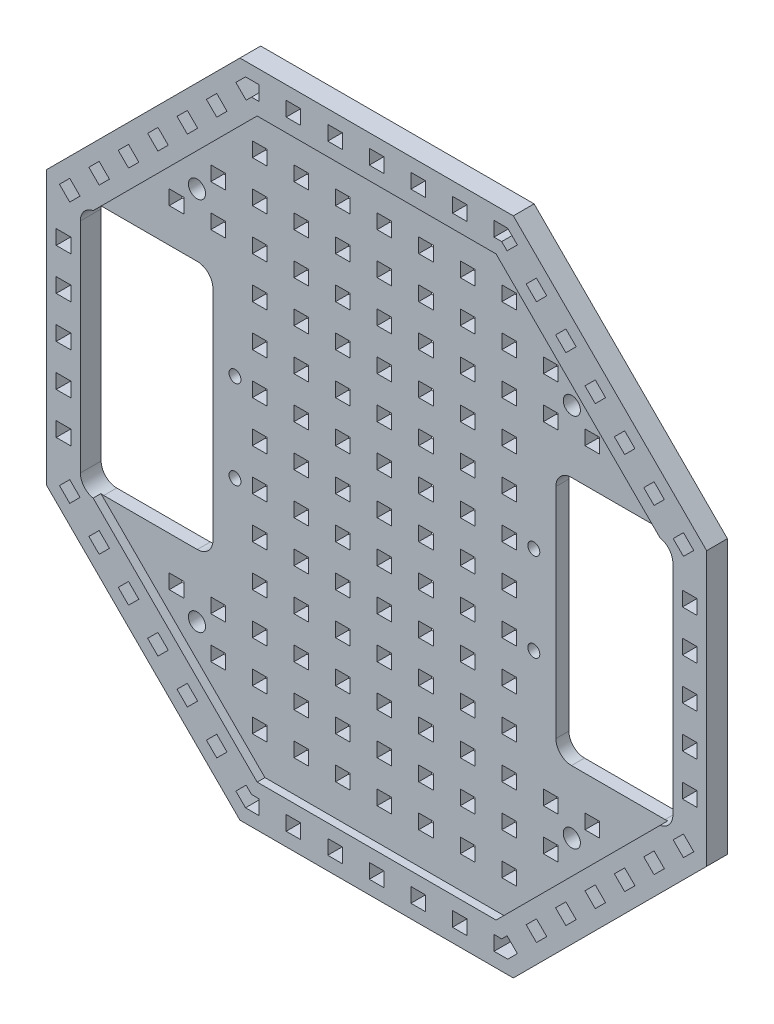
SolidWorks part; units mm, degrees
ref_plane "Plano frontal" through (0, 0, 0) normal (0, 0, 1) x (1, 0, 0)
ref_plane "Plano superior" through (0, 0, 0) normal (0, 1, 0) x (1, 0, 0)
ref_plane "Plano direito" through (0, 0, 0) normal (1, 0, 0) x (0, 0, -1)
sketch "Esboço1" plane through (0, 0, 0) normal (0, 0, 1) x (1, 0, 0)
  line L1 (63.5, -26.3026) -> (63.5, 26.3026)
  line L2 (63.5, 26.3026) -> (26.3026, 63.5)
  line L3 (26.3026, 63.5) -> (-26.3026, 63.5)
  line L4 (-26.3026, 63.5) -> (-63.5, 26.3026)
  line L5 (-63.5, 26.3026) -> (-63.5, -26.3026)
  line L6 (-63.5, -26.3026) -> (-26.3026, -63.5)
  line L7 (-26.3026, -63.5) -> (26.3026, -63.5)
  line L8 (26.3026, -63.5) -> (63.5, -26.3026)
  circle A0 centre (0, 0) radius 63.5 construction
  dimension "D1" = 127
extrude "Ressalto-extrusão1" add sketch "Esboço1" along normal blind 2.5
sketch "Esboço3"
sketch "Esboço2" plane through (0, 0, 0) normal (0, 0, -1) x (-1, 0, 0)
  line L0 (-45, 0) -> (45, 0) construction
  line L1 (-28.75, 0) -> (28.75, 0) construction
  line L2 (28.75, 0) -> (28.75, 8.5) construction
  line L3 (0, 0) -> (0, 75.734) construction
  line L4 (54, 24) -> (36, 24)
  line L5 (57, 21) -> (57, -21)
  line L6 (54, -24) -> (36, -24)
  line L7 (33, 21) -> (33, -21)
  line L8 (57, 24) -> (33, -24) construction
  line L9 (57, -24) -> (33, 24) construction
  line L10 (-57, -24) -> (-33, 24) construction
  line L11 (-57, 24) -> (-33, -24) construction
  line L12 (-28.75, 0) -> (-28.75, 8.5) construction
  line L13 (-33, 21) -> (-33, -21)
  line L14 (-54, -24) -> (-36, -24)
  line L15 (-57, 21) -> (-57, -21)
  line L16 (-54, 24) -> (-36, 24)
  line L17 (0, 0) -> (0, -57) construction
  circle A0 centre (28.75, 8.5) radius 1.15
  circle A1 centre (28.75, -8.5) radius 1.15
  arc A2 (36, 24) -> (33, 21) centre (36, 21) ccw
  arc A3 (36, -24) -> (33, -21) centre (36, -21) cw
  arc A4 (57, -21) -> (54, -24) centre (54, -21) cw
  arc A5 (54, 24) -> (57, 21) centre (54, 21) cw
  arc A6 (-54, 24) -> (-57, 21) centre (-54, 21) ccw
  arc A7 (-57, -21) -> (-54, -24) centre (-54, -21) ccw
  arc A8 (-36, -24) -> (-33, -21) centre (-36, -21) ccw
  arc A9 (-36, 24) -> (-33, 21) centre (-36, 21) cw
  circle A10 centre (-28.75, -8.5) radius 1.15
  circle A11 centre (-28.75, 8.5) radius 1.15
  dimension "D6" = 3
  dimension "D1" = 45
  dimension "D2" = 48
  dimension "D3" = 24
  dimension "D4" = 28.75
  dimension "D5" = 8.5
  dimension "D7" = 57
extrude "Corte-extrusão1" cut sketch "Esboço2" against normal through all
sketch "Esboço4" plane through (0, 0, 0) normal (0, 0, -1) x (-1, 0, 0)
  line L0 (0, 0) -> (36.0624, 36.0624) construction
  circle A0 centre (0, 0) radius 51 construction
  circle A1 centre (36.0624, -36.0624) radius 1.65
  circle A2 centre (36.0624, 36.0624) radius 1.65
  circle A3 centre (-36.0624, -36.0624) radius 1.65
  circle A4 centre (-36.0624, 36.0624) radius 1.65
  point P7 (0, 0)
  point P14 (0, 0)
  point P15 (0, 0)
  dimension "D1" = 4
extrude "Corte-extrusão2" cut sketch "Esboço4" against normal blind 40.5
sketch "Esboço5" plane through (0, 0, 2.5) normal (0, 0, 1) x (1, 0, 0)
  line L0 (23.6102, -57) -> (57, -23.6102) construction
  line L1 (57, -21) -> (57, 21)
  line L2 (57, 23.6102) -> (23.6102, 57) construction
  line L3 (23.6102, 57) -> (-23.6102, 57) construction
  line L4 (-23.6102, 57) -> (-57, 23.6102) construction
  line L5 (-57, 21) -> (-57, -21)
  line L6 (-57, -23.6102) -> (-23.6102, -57) construction
  line L7 (-23.6102, -57) -> (23.6102, -57) construction
  line L8 (26.3026, -63.5) -> (63.5, -26.3026)
  line L9 (63.5, -26.3026) -> (63.5, 26.3026)
  line L10 (63.5, 26.3026) -> (26.3026, 63.5)
  line L11 (26.3026, 63.5) -> (-26.3026, 63.5)
  line L12 (-26.3026, 63.5) -> (-63.5, 26.3026)
  line L13 (-63.5, 26.3026) -> (-63.5, -26.3026)
  line L14 (-63.5, -26.3026) -> (-26.3026, -63.5)
  line L15 (-26.3026, -63.5) -> (26.3026, -63.5)
  line L16 (26.3026, -63.5) -> (63.5, -26.3026)
  line L17 (63.5, -26.3026) -> (63.5, 26.3026)
  line L18 (63.5, 26.3026) -> (26.3026, 63.5)
  line L19 (26.3026, 63.5) -> (-26.3026, 63.5)
  line L20 (-26.3026, 63.5) -> (-63.5, 26.3026)
  line L21 (-63.5, 26.3026) -> (-63.5, -26.3026)
  line L22 (-63.5, -26.3026) -> (-26.3026, -63.5)
  line L23 (-26.3026, -63.5) -> (26.3026, -63.5)
  line L24 (-22.9889, 55.5) -> (-54.5374, 23.9515)
  line L25 (-22.9889, 55.5) -> (-55.5, 22.9889) construction
  line L26 (-54.5374, -23.9515) -> (-22.9889, -55.5)
  line L27 (-22.9889, -55.5) -> (22.9889, -55.5)
  line L28 (22.9889, -55.5) -> (54.5374, -23.9515)
  line L29 (-55.5, -22.9889) -> (-22.9889, -55.5) construction
  line L30 (54.5374, 23.9515) -> (22.9889, 55.5)
  line L31 (22.9889, 55.5) -> (-22.9889, 55.5)
  line L32 (22.9889, -55.5) -> (55.5, -22.9889) construction
  line L33 (57, -23.6102) -> (57, 23.6102) construction
  line L34 (55.5, 22.9889) -> (22.9889, 55.5) construction
  line L35 (55.5, -22.9889) -> (55.5, 22.9889) construction
  line L43 (-55.5, 22.9889) -> (-55.5, -22.9889) construction
  line L44 (-57, 23.6102) -> (-57, -23.6102) construction
  arc A2 (54.5374, -23.9515) -> (57, -21) centre (54, -21) ccw
  arc A3 (57, 21) -> (54.5374, 23.9515) centre (54, 21) ccw
  arc A5 (-54.5374, 23.9515) -> (-57, 21) centre (-54, 21) ccw
  arc A7 (-57, -21) -> (-54.5374, -23.9515) centre (-54, -21) ccw
  dimension "D1" = 0
  dimension "D2" = 6.5
  dimension "D3" = 1.5
extrude "Ressalto-extrusão2" add sketch "Esboço5" along normal blind 1.5
sketch "Esboço6" plane through (0, 0, 0) normal (0, 0, -1) x (-1, 0, 0)
  line L0 (-44.9013, -44.9013) -> (-42.0729, -42.0729) construction
  line L1 (-47.7297, -34.4361) -> (-49.7096, -36.416)
  line L2 (-42.0729, -40.093) -> (-44.0528, -42.0729)
  line L3 (-42.0729, -40.093) -> (-40.093, -42.0729)
  line L4 (-40.093, -42.0729) -> (-42.0729, -44.0528)
  line L5 (-44.0528, -42.0729) -> (-42.0729, -44.0528)
  line L6 (-42.0729, -40.093) -> (-42.0729, -44.0528) construction
  line L7 (-40.093, -42.0729) -> (-44.0528, -42.0729) construction
  line L8 (-47.7297, -34.4361) -> (-45.7498, -36.416)
  line L9 (-45.7498, -36.416) -> (-47.7297, -38.3959)
  line L10 (-49.7096, -36.416) -> (-47.7297, -38.3959)
  line L11 (-47.7297, -34.4361) -> (-47.7297, -38.3959) construction
  line L12 (-45.7498, -36.416) -> (-49.7096, -36.416) construction
  line L13 (-53.3866, -28.7792) -> (-55.3665, -30.7591)
  line L14 (-53.3866, -28.7792) -> (-51.4067, -30.7591)
  line L15 (-51.4067, -30.7591) -> (-53.3866, -32.739)
  line L16 (-55.3665, -30.7591) -> (-53.3866, -32.739)
  line L17 (-53.3866, -28.7792) -> (-53.3866, -32.739) construction
  line L18 (-51.4067, -30.7591) -> (-55.3665, -30.7591) construction
  line L19 (-59.0434, -23.1224) -> (-61.0233, -25.1023)
  line L20 (-59.0434, -23.1224) -> (-57.0635, -25.1023)
  line L21 (-57.0635, -25.1023) -> (-59.0434, -27.0822)
  line L22 (-61.0233, -25.1023) -> (-59.0434, -27.0822)
  line L23 (-59.0434, -23.1224) -> (-59.0434, -27.0822) construction
  line L24 (-57.0635, -25.1023) -> (-61.0233, -25.1023) construction
  line L25 (-63.5, 0) -> (-57, 0) construction
  line L26 (-30.7591, -51.4067) -> (-30.7591, -55.3665) construction
  line L27 (-28.7792, -53.3866) -> (-32.739, -53.3866) construction
  line L28 (-36.416, -45.7498) -> (-36.416, -49.7096) construction
  line L29 (-34.4361, -47.7297) -> (-38.3959, -47.7297) construction
  line L30 (-42.0729, -40.093) -> (-42.0729, -44.0528) construction
  line L31 (-40.093, -42.0729) -> (-44.0528, -42.0729) construction
  line L32 (-25.2256, -60.9) -> (-27.0822, -59.0434)
  line L33 (-25.1023, -57.0635) -> (-27.0822, -59.0434)
  line L34 (-58.85, -6.6) -> (-61.65, -6.6)
  line L35 (-30.7591, -55.3665) -> (-32.739, -53.3866)
  line L36 (-30.7591, -51.4067) -> (-32.739, -53.3866)
  line L37 (-28.7792, -53.3866) -> (-30.7591, -51.4067)
  line L38 (-28.7792, -53.3866) -> (-30.7591, -55.3665)
  line L39 (-36.416, -49.7096) -> (-38.3959, -47.7297)
  line L40 (-36.416, -45.7498) -> (-38.3959, -47.7297)
  line L41 (-34.4361, -47.7297) -> (-36.416, -45.7498)
  line L42 (-34.4361, -47.7297) -> (-36.416, -49.7096)
  line L43 (0, -63.5) -> (0, -59.5) construction
  line L44 (-6.6, -58.1) -> (-9.4, -58.1)
  line L45 (1.4, -58.1) -> (-1.4, -58.1)
  line L46 (1.4, -58.1) -> (1.4, -60.9)
  line L47 (1.4, -60.9) -> (-1.4, -60.9)
  line L48 (-1.4, -58.1) -> (-1.4, -60.9)
  line L49 (1.4, -58.1) -> (-1.4, -60.9) construction
  line L50 (1.4, -60.9) -> (-1.4, -58.1) construction
  line L51 (-6.6, -58.1) -> (-6.6, -60.9)
  line L52 (-6.6, -60.9) -> (-9.4, -60.9)
  line L53 (-9.4, -58.1) -> (-9.4, -60.9)
  line L54 (-6.6, -58.1) -> (-9.4, -60.9) construction
  line L55 (-6.6, -60.9) -> (-9.4, -58.1) construction
  line L56 (-14.6, -58.1) -> (-17.4, -58.1)
  line L57 (-14.6, -58.1) -> (-14.6, -60.9)
  line L58 (-14.6, -60.9) -> (-17.4, -60.9)
  line L59 (-17.4, -58.1) -> (-17.4, -60.9)
  line L60 (-14.6, -58.1) -> (-17.4, -60.9) construction
  line L61 (-14.6, -60.9) -> (-17.4, -58.1) construction
  line L62 (-22.6, -58.1) -> (-24.0658, -58.1)
  line L63 (-22.6, -58.1) -> (-22.6, -60.9)
  line L64 (-22.6, -60.9) -> (-25.2256, -60.9)
  line L65 (-58.85, 1.4) -> (-61.65, 1.4)
  line L66 (-58.85, 1.4) -> (-58.85, -1.4)
  line L67 (-58.85, -1.4) -> (-61.65, -1.4)
  line L68 (-61.65, 1.4) -> (-61.65, -1.4)
  line L69 (-58.85, 1.4) -> (-61.65, -1.4) construction
  line L70 (58.85, -17.4) -> (61.65, -14.6) construction
  line L71 (9.4, 1.4) -> (6.6, -1.4) construction
  line L72 (16, 24) -> (0, 24) construction
  line L73 (0, 24) -> (-16, 24) construction
  line L74 (-24.0658, -58.1) -> (-25.1023, -57.0635)
  line L75 (6.6, 25.4) -> (6.6, 22.6)
  line L76 (9.4, 22.6) -> (6.6, 22.6)
  line L77 (-25.4, 46.6) -> (-22.6, 49.4) construction
  line L78 (9.4, 25.4) -> (6.6, 22.6) construction
  line L79 (-58.85, -1.4) -> (-61.65, 1.4) construction
  line L80 (-58.85, -6.6) -> (-58.85, -9.4)
  line L81 (-58.85, -9.4) -> (-61.65, -9.4)
  line L82 (-61.65, -6.6) -> (-61.65, -9.4)
  line L83 (-58.85, -6.6) -> (-61.65, -9.4) construction
  line L84 (-58.85, -9.4) -> (-61.65, -6.6) construction
  line L85 (-58.85, -14.6) -> (-61.65, -14.6)
  line L86 (-58.85, -14.6) -> (-58.85, -17.4)
  line L87 (-58.85, -17.4) -> (-61.65, -17.4)
  line L88 (-61.65, -14.6) -> (-61.65, -17.4)
  line L89 (-58.85, -14.6) -> (-61.65, -17.4) construction
  line L90 (-58.85, -17.4) -> (-61.65, -14.6) construction
  line L91 (9.4, 22.6) -> (6.6, 25.4) construction
  line L92 (0, 0) -> (0, 63.5) construction
  line L93 (-25.4, 49.4) -> (-22.6, 46.6) construction
  line L94 (58.85, -14.6) -> (61.65, -17.4) construction
  line L95 (58.85, -9.4) -> (61.65, -6.6) construction
  line L96 (58.85, -6.6) -> (61.65, -9.4) construction
  line L97 (58.85, -1.4) -> (61.65, 1.4) construction
  line L98 (58.85, 1.4) -> (61.65, -1.4) construction
  line L99 (14.6, -60.9) -> (17.4, -58.1) construction
  line L100 (14.6, -58.1) -> (17.4, -60.9) construction
  line L101 (6.6, -60.9) -> (9.4, -58.1) construction
  line L102 (6.6, -58.1) -> (9.4, -60.9) construction
  line L103 (40.093, -42.0729) -> (44.0528, -42.0729) construction
  line L104 (42.0729, -40.093) -> (42.0729, -44.0528) construction
  line L105 (34.4361, -47.7297) -> (38.3959, -47.7297) construction
  line L106 (36.416, -45.7498) -> (36.416, -49.7096) construction
  line L107 (28.7792, -53.3866) -> (32.739, -53.3866) construction
  line L108 (30.7591, -51.4067) -> (30.7591, -55.3665) construction
  line L109 (63.5, 0) -> (57, 0) construction
  line L110 (57.0635, -25.1023) -> (61.0233, -25.1023) construction
  line L111 (59.0434, -23.1224) -> (59.0434, -27.0822) construction
  line L112 (51.4067, -30.7591) -> (55.3665, -30.7591) construction
  line L113 (53.3866, -28.7792) -> (53.3866, -32.739) construction
  line L114 (45.7498, -36.416) -> (49.7096, -36.416) construction
  line L115 (47.7297, -34.4361) -> (47.7297, -38.3959) construction
  line L116 (40.093, -42.0729) -> (44.0528, -42.0729) construction
  line L117 (42.0729, -40.093) -> (42.0729, -44.0528) construction
  line L118 (44.9013, -44.9013) -> (42.0729, -42.0729) construction
  line L119 (61.65, -14.6) -> (61.65, -17.4)
  line L120 (58.85, -17.4) -> (61.65, -17.4)
  line L121 (58.85, -14.6) -> (58.85, -17.4)
  line L122 (58.85, -14.6) -> (61.65, -14.6)
  line L123 (61.65, -6.6) -> (61.65, -9.4)
  line L124 (58.85, -9.4) -> (61.65, -9.4)
  line L125 (58.85, -6.6) -> (58.85, -9.4)
  line L126 (24.0658, -58.1) -> (25.1023, -57.0635)
  line L127 (61.65, 1.4) -> (61.65, -1.4)
  line L128 (58.85, -1.4) -> (61.65, -1.4)
  line L129 (58.85, 1.4) -> (58.85, -1.4)
  line L130 (58.85, 1.4) -> (61.65, 1.4)
  line L131 (22.6, -60.9) -> (25.2256, -60.9)
  line L132 (22.6, -58.1) -> (22.6, -60.9)
  line L133 (22.6, -58.1) -> (24.0658, -58.1)
  line L134 (17.4, -58.1) -> (17.4, -60.9)
  line L135 (14.6, -60.9) -> (17.4, -60.9)
  line L136 (14.6, -58.1) -> (14.6, -60.9)
  line L137 (14.6, -58.1) -> (17.4, -58.1)
  line L138 (9.4, -58.1) -> (9.4, -60.9)
  line L139 (6.6, -60.9) -> (9.4, -60.9)
  line L140 (6.6, -58.1) -> (6.6, -60.9)
  line L141 (6.6, -58.1) -> (9.4, -58.1)
  line L142 (34.4361, -47.7297) -> (36.416, -49.7096)
  line L143 (40.093, -42.0729) -> (42.0729, -44.0528)
  line L144 (42.0729, -40.093) -> (44.0528, -42.0729)
  line L145 (34.4361, -47.7297) -> (36.416, -45.7498)
  line L146 (36.416, -45.7498) -> (38.3959, -47.7297)
  line L147 (36.416, -49.7096) -> (38.3959, -47.7297)
  line L148 (28.7792, -53.3866) -> (30.7591, -55.3665)
  line L149 (28.7792, -53.3866) -> (30.7591, -51.4067)
  line L150 (30.7591, -51.4067) -> (32.739, -53.3866)
  line L151 (30.7591, -55.3665) -> (32.739, -53.3866)
  line L152 (58.85, -6.6) -> (61.65, -6.6)
  line L153 (25.1023, -57.0635) -> (27.0822, -59.0434)
  line L154 (25.2256, -60.9) -> (27.0822, -59.0434)
  line L155 (61.0233, -25.1023) -> (59.0434, -27.0822)
  line L156 (57.0635, -25.1023) -> (59.0434, -27.0822)
  line L157 (59.0434, -23.1224) -> (57.0635, -25.1023)
  line L158 (59.0434, -23.1224) -> (61.0233, -25.1023)
  line L159 (55.3665, -30.7591) -> (53.3866, -32.739)
  line L160 (51.4067, -30.7591) -> (53.3866, -32.739)
  line L161 (53.3866, -28.7792) -> (51.4067, -30.7591)
  line L162 (53.3866, -28.7792) -> (55.3665, -30.7591)
  line L163 (49.7096, -36.416) -> (47.7297, -38.3959)
  line L164 (45.7498, -36.416) -> (47.7297, -38.3959)
  line L165 (47.7297, -34.4361) -> (45.7498, -36.416)
  line L166 (44.0528, -42.0729) -> (42.0729, -44.0528)
  line L167 (42.0729, -40.093) -> (40.093, -42.0729)
  line L168 (47.7297, -34.4361) -> (49.7096, -36.416)
  line L169 (44.9013, 44.9013) -> (42.0729, 42.0729) construction
  line L170 (42.0729, 40.093) -> (42.0729, 44.0528) construction
  line L171 (40.093, 42.0729) -> (44.0528, 42.0729) construction
  line L172 (47.7297, 34.4361) -> (47.7297, 38.3959) construction
  line L173 (45.7498, 36.416) -> (49.7096, 36.416) construction
  line L174 (53.3866, 28.7792) -> (53.3866, 32.739) construction
  line L175 (51.4067, 30.7591) -> (55.3665, 30.7591) construction
  line L176 (59.0434, 23.1224) -> (59.0434, 27.0822) construction
  line L177 (57.0635, 25.1023) -> (61.0233, 25.1023) construction
  line L178 (30.7591, 51.4067) -> (30.7591, 55.3665) construction
  line L179 (28.7792, 53.3866) -> (32.739, 53.3866) construction
  line L180 (36.416, 45.7498) -> (36.416, 49.7096) construction
  line L181 (34.4361, 47.7297) -> (38.3959, 47.7297) construction
  line L182 (42.0729, 40.093) -> (42.0729, 44.0528) construction
  line L183 (40.093, 42.0729) -> (44.0528, 42.0729) construction
  line L184 (6.6, 58.1) -> (9.4, 60.9) construction
  line L185 (6.6, 60.9) -> (9.4, 58.1) construction
  line L186 (14.6, 58.1) -> (17.4, 60.9) construction
  line L187 (14.6, 60.9) -> (17.4, 58.1) construction
  line L188 (58.85, 6.6) -> (61.65, 9.4) construction
  line L189 (58.85, 9.4) -> (61.65, 6.6) construction
  line L190 (58.85, 14.6) -> (61.65, 17.4) construction
  line L191 (-58.85, 17.4) -> (-61.65, 14.6) construction
  line L192 (-58.85, 14.6) -> (-61.65, 17.4) construction
  line L193 (-58.85, 9.4) -> (-61.65, 6.6) construction
  line L194 (-58.85, 6.6) -> (-61.65, 9.4) construction
  line L195 (58.85, 17.4) -> (61.65, 14.6) construction
  line L196 (-14.6, 60.9) -> (-17.4, 58.1) construction
  line L197 (-14.6, 58.1) -> (-17.4, 60.9) construction
  line L198 (-6.6, 60.9) -> (-9.4, 58.1) construction
  line L199 (-6.6, 58.1) -> (-9.4, 60.9) construction
  line L200 (1.4, 60.9) -> (-1.4, 58.1) construction
  line L201 (1.4, 58.1) -> (-1.4, 60.9) construction
  line L202 (0, 63.5) -> (0, 59.5) construction
  line L203 (-40.093, 42.0729) -> (-44.0528, 42.0729) construction
  line L204 (-42.0729, 40.093) -> (-42.0729, 44.0528) construction
  line L205 (-34.4361, 47.7297) -> (-38.3959, 47.7297) construction
  line L206 (-36.416, 45.7498) -> (-36.416, 49.7096) construction
  line L207 (-28.7792, 53.3866) -> (-32.739, 53.3866) construction
  line L208 (-30.7591, 51.4067) -> (-30.7591, 55.3665) construction
  line L209 (-57.0635, 25.1023) -> (-61.0233, 25.1023) construction
  line L210 (-59.0434, 23.1224) -> (-59.0434, 27.0822) construction
  line L211 (-51.4067, 30.7591) -> (-55.3665, 30.7591) construction
  line L212 (-53.3866, 28.7792) -> (-53.3866, 32.739) construction
  line L213 (-45.7498, 36.416) -> (-49.7096, 36.416) construction
  line L214 (-47.7297, 34.4361) -> (-47.7297, 38.3959) construction
  line L215 (-40.093, 42.0729) -> (-44.0528, 42.0729) construction
  line L216 (-42.0729, 40.093) -> (-42.0729, 44.0528) construction
  line L217 (-44.9013, 44.9013) -> (-42.0729, 42.0729) construction
  line L218 (47.7297, 34.4361) -> (49.7096, 36.416)
  line L219 (42.0729, 40.093) -> (44.0528, 42.0729)
  line L220 (42.0729, 40.093) -> (40.093, 42.0729)
  line L221 (40.093, 42.0729) -> (42.0729, 44.0528)
  line L222 (44.0528, 42.0729) -> (42.0729, 44.0528)
  line L223 (47.7297, 34.4361) -> (45.7498, 36.416)
  line L224 (45.7498, 36.416) -> (47.7297, 38.3959)
  line L225 (49.7096, 36.416) -> (47.7297, 38.3959)
  line L226 (53.3866, 28.7792) -> (55.3665, 30.7591)
  line L227 (53.3866, 28.7792) -> (51.4067, 30.7591)
  line L228 (51.4067, 30.7591) -> (53.3866, 32.739)
  line L229 (55.3665, 30.7591) -> (53.3866, 32.739)
  line L230 (59.0434, 23.1224) -> (61.0233, 25.1023)
  line L231 (59.0434, 23.1224) -> (57.0635, 25.1023)
  line L232 (57.0635, 25.1023) -> (59.0434, 27.0822)
  line L233 (61.0233, 25.1023) -> (59.0434, 27.0822)
  line L234 (25.2256, 60.9) -> (27.0822, 59.0434)
  line L235 (25.1023, 57.0635) -> (27.0822, 59.0434)
  line L236 (58.85, 6.6) -> (61.65, 6.6)
  line L237 (30.7591, 55.3665) -> (32.739, 53.3866)
  line L238 (30.7591, 51.4067) -> (32.739, 53.3866)
  line L239 (28.7792, 53.3866) -> (30.7591, 51.4067)
  line L240 (28.7792, 53.3866) -> (30.7591, 55.3665)
  line L241 (36.416, 49.7096) -> (38.3959, 47.7297)
  line L242 (36.416, 45.7498) -> (38.3959, 47.7297)
  line L243 (34.4361, 47.7297) -> (36.416, 45.7498)
  line L244 (34.4361, 47.7297) -> (36.416, 49.7096)
  line L245 (6.6, 58.1) -> (9.4, 58.1)
  line L246 (6.6, 58.1) -> (6.6, 60.9)
  line L247 (6.6, 60.9) -> (9.4, 60.9)
  line L248 (9.4, 58.1) -> (9.4, 60.9)
  line L249 (14.6, 58.1) -> (17.4, 58.1)
  line L250 (14.6, 58.1) -> (14.6, 60.9)
  line L251 (14.6, 60.9) -> (17.4, 60.9)
  line L252 (17.4, 58.1) -> (17.4, 60.9)
  line L253 (22.6, 58.1) -> (24.0658, 58.1)
  line L254 (22.6, 58.1) -> (22.6, 60.9)
  line L255 (22.6, 60.9) -> (25.2256, 60.9)
  line L256 (24.0658, 58.1) -> (25.1023, 57.0635)
  line L257 (58.85, 6.6) -> (58.85, 9.4)
  line L258 (58.85, 9.4) -> (61.65, 9.4)
  line L259 (61.65, 6.6) -> (61.65, 9.4)
  line L260 (58.85, 14.6) -> (61.65, 14.6)
  line L261 (58.85, 14.6) -> (58.85, 17.4)
  line L262 (58.85, 17.4) -> (61.65, 17.4)
  line L263 (61.65, 14.6) -> (61.65, 17.4)
  line L264 (-61.65, 14.6) -> (-61.65, 17.4)
  line L265 (-58.85, 17.4) -> (-61.65, 17.4)
  line L266 (-58.85, 14.6) -> (-58.85, 17.4)
  line L267 (-58.85, 14.6) -> (-61.65, 14.6)
  line L268 (-61.65, 6.6) -> (-61.65, 9.4)
  line L269 (-58.85, 9.4) -> (-61.65, 9.4)
  line L270 (-58.85, 6.6) -> (-58.85, 9.4)
  line L271 (-24.0658, 58.1) -> (-25.1023, 57.0635)
  line L272 (-22.6, 60.9) -> (-25.2256, 60.9)
  line L273 (-22.6, 58.1) -> (-22.6, 60.9)
  line L274 (-22.6, 58.1) -> (-24.0658, 58.1)
  line L275 (-17.4, 58.1) -> (-17.4, 60.9)
  line L276 (-14.6, 60.9) -> (-17.4, 60.9)
  line L277 (-14.6, 58.1) -> (-14.6, 60.9)
  line L278 (-14.6, 58.1) -> (-17.4, 58.1)
  line L279 (-9.4, 58.1) -> (-9.4, 60.9)
  line L280 (-6.6, 60.9) -> (-9.4, 60.9)
  line L281 (-6.6, 58.1) -> (-6.6, 60.9)
  line L282 (-1.4, 58.1) -> (-1.4, 60.9)
  line L283 (1.4, 60.9) -> (-1.4, 60.9)
  line L284 (1.4, 58.1) -> (1.4, 60.9)
  line L285 (1.4, 58.1) -> (-1.4, 58.1)
  line L286 (-6.6, 58.1) -> (-9.4, 58.1)
  line L287 (-34.4361, 47.7297) -> (-36.416, 49.7096)
  line L288 (-40.093, 42.0729) -> (-42.0729, 44.0528)
  line L289 (-42.0729, 40.093) -> (-44.0528, 42.0729)
  line L290 (-34.4361, 47.7297) -> (-36.416, 45.7498)
  line L291 (-36.416, 45.7498) -> (-38.3959, 47.7297)
  line L292 (-36.416, 49.7096) -> (-38.3959, 47.7297)
  line L293 (-28.7792, 53.3866) -> (-30.7591, 55.3665)
  line L294 (-28.7792, 53.3866) -> (-30.7591, 51.4067)
  line L295 (-30.7591, 51.4067) -> (-32.739, 53.3866)
  line L296 (-30.7591, 55.3665) -> (-32.739, 53.3866)
  line L297 (-58.85, 6.6) -> (-61.65, 6.6)
  line L298 (-25.1023, 57.0635) -> (-27.0822, 59.0434)
  line L299 (-25.2256, 60.9) -> (-27.0822, 59.0434)
  line L300 (-61.0233, 25.1023) -> (-59.0434, 27.0822)
  line L301 (-57.0635, 25.1023) -> (-59.0434, 27.0822)
  line L302 (-59.0434, 23.1224) -> (-57.0635, 25.1023)
  line L303 (-59.0434, 23.1224) -> (-61.0233, 25.1023)
  line L304 (-55.3665, 30.7591) -> (-53.3866, 32.739)
  line L305 (-51.4067, 30.7591) -> (-53.3866, 32.739)
  line L306 (-53.3866, 28.7792) -> (-51.4067, 30.7591)
  line L307 (-53.3866, 28.7792) -> (-55.3665, 30.7591)
  line L308 (-49.7096, 36.416) -> (-47.7297, 38.3959)
  line L309 (-45.7498, 36.416) -> (-47.7297, 38.3959)
  line L310 (-47.7297, 34.4361) -> (-45.7498, 36.416)
  line L311 (-44.0528, 42.0729) -> (-42.0729, 44.0528)
  line L312 (-42.0729, 40.093) -> (-40.093, 42.0729)
  line L313 (-47.7297, 34.4361) -> (-49.7096, 36.416)
  line L314 (-17.4, 46.6) -> (-14.6, 49.4) construction
  line L315 (1.4, 1.4) -> (-1.4, 1.4)
  line L316 (1.4, 1.4) -> (1.4, -1.4)
  line L317 (1.4, -1.4) -> (-1.4, -1.4)
  line L318 (-1.4, 1.4) -> (-1.4, -1.4)
  line L319 (1.4, 1.4) -> (-1.4, -1.4) construction
  line L320 (1.4, -1.4) -> (-1.4, 1.4) construction
  line L321 (9.4, -1.4) -> (6.6, 1.4) construction
  line L322 (9.4, 1.4) -> (9.4, -1.4)
  line L323 (9.4, 1.4) -> (6.6, 1.4)
  line L324 (6.6, 1.4) -> (6.6, -1.4)
  line L325 (9.4, -1.4) -> (6.6, -1.4)
  line L326 (17.4, 1.4) -> (14.6, -1.4) construction
  line L327 (17.4, -1.4) -> (14.6, 1.4) construction
  line L328 (17.4, 1.4) -> (17.4, -1.4)
  line L329 (17.4, 1.4) -> (14.6, 1.4)
  line L330 (14.6, 1.4) -> (14.6, -1.4)
  line L331 (17.4, -1.4) -> (14.6, -1.4)
  line L332 (25.4, 1.4) -> (22.6, -1.4) construction
  line L333 (25.4, -1.4) -> (22.6, 1.4) construction
  line L334 (25.4, 1.4) -> (25.4, -1.4)
  line L335 (25.4, 1.4) -> (22.6, 1.4)
  line L336 (22.6, 1.4) -> (22.6, -1.4)
  line L337 (25.4, -1.4) -> (22.6, -1.4)
  line L338 (9.4, 25.4) -> (9.4, 22.6)
  line L339 (9.4, 25.4) -> (6.6, 25.4)
  line L340 (-9.4, 25.4) -> (-9.4, 22.6)
  line L341 (-6.6, 22.6) -> (-9.4, 22.6)
  line L342 (-6.6, 25.4) -> (-9.4, 22.6) construction
  line L343 (-6.6, 22.6) -> (-9.4, 25.4) construction
  line L344 (-6.6, 25.4) -> (-6.6, 22.6)
  line L345 (-6.6, 25.4) -> (-9.4, 25.4)
  line L346 (0, 0) -> (76.7252, 0) construction
  line L347 (-6.6, -22.6) -> (-9.4, -25.4) construction
  line L348 (-6.6, -25.4) -> (-9.4, -22.6) construction
  line L349 (-6.6, -25.4) -> (-9.4, -25.4)
  line L350 (-6.6, -25.4) -> (-6.6, -22.6)
  line L351 (-6.6, -22.6) -> (-9.4, -22.6)
  line L352 (-9.4, -25.4) -> (-9.4, -22.6)
  line L353 (9.4, -22.6) -> (6.6, -25.4) construction
  line L354 (9.4, -25.4) -> (6.6, -22.6) construction
  line L355 (9.4, -25.4) -> (6.6, -25.4)
  line L356 (9.4, 9.4) -> (6.6, 6.6) construction
  line L357 (9.4, 6.6) -> (6.6, 9.4) construction
  line L358 (9.4, 9.4) -> (9.4, 6.6)
  line L359 (9.4, 9.4) -> (6.6, 9.4)
  line L360 (6.6, 9.4) -> (6.6, 6.6)
  line L361 (9.4, 6.6) -> (6.6, 6.6)
  line L362 (17.4, 9.4) -> (14.6, 6.6) construction
  line L363 (17.4, 6.6) -> (14.6, 9.4) construction
  line L364 (17.4, 9.4) -> (17.4, 6.6)
  line L365 (17.4, 9.4) -> (14.6, 9.4)
  line L366 (14.6, 9.4) -> (14.6, 6.6)
  line L367 (17.4, 6.6) -> (14.6, 6.6)
  line L368 (25.4, 9.4) -> (22.6, 6.6) construction
  line L369 (25.4, 6.6) -> (22.6, 9.4) construction
  line L370 (25.4, 9.4) -> (25.4, 6.6)
  line L371 (25.4, 9.4) -> (22.6, 9.4)
  line L372 (22.6, 9.4) -> (22.6, 6.6)
  line L373 (25.4, 6.6) -> (22.6, 6.6)
  line L374 (9.4, -25.4) -> (9.4, -22.6)
  line L375 (9.4, -22.6) -> (6.6, -22.6)
  line L376 (6.6, -25.4) -> (6.6, -22.6)
  line L392 (9.4, 17.4) -> (6.6, 14.6) construction
  line L393 (9.4, 14.6) -> (6.6, 17.4) construction
  line L394 (9.4, 17.4) -> (9.4, 14.6)
  line L395 (9.4, 17.4) -> (6.6, 17.4)
  line L396 (6.6, 17.4) -> (6.6, 14.6)
  line L397 (9.4, 14.6) -> (6.6, 14.6)
  line L398 (17.4, 17.4) -> (14.6, 14.6) construction
  line L399 (17.4, 14.6) -> (14.6, 17.4) construction
  line L400 (17.4, 17.4) -> (17.4, 14.6)
  line L401 (17.4, 17.4) -> (14.6, 17.4)
  line L402 (14.6, 17.4) -> (14.6, 14.6)
  line L403 (17.4, 14.6) -> (14.6, 14.6)
  line L404 (25.4, 17.4) -> (22.6, 14.6) construction
  line L405 (25.4, 14.6) -> (22.6, 17.4) construction
  line L406 (25.4, 17.4) -> (25.4, 14.6)
  line L407 (25.4, 17.4) -> (22.6, 17.4)
  line L408 (22.6, 17.4) -> (22.6, 14.6)
  line L409 (25.4, 14.6) -> (22.6, 14.6)
  line L434 (17.4, 25.4) -> (14.6, 22.6) construction
  line L435 (17.4, 22.6) -> (14.6, 25.4) construction
  line L436 (17.4, 25.4) -> (17.4, 22.6)
  line L437 (17.4, 25.4) -> (14.6, 25.4)
  line L438 (14.6, 25.4) -> (14.6, 22.6)
  line L439 (17.4, 22.6) -> (14.6, 22.6)
  line L440 (25.4, 25.4) -> (22.6, 22.6) construction
  line L441 (25.4, 22.6) -> (22.6, 25.4) construction
  line L442 (25.4, 25.4) -> (25.4, 22.6)
  line L443 (25.4, 25.4) -> (22.6, 25.4)
  line L444 (22.6, 25.4) -> (22.6, 22.6)
  line L445 (25.4, 22.6) -> (22.6, 22.6)
  line L464 (9.4, 33.4) -> (6.6, 30.6) construction
  line L465 (9.4, 30.6) -> (6.6, 33.4) construction
  line L466 (9.4, 33.4) -> (9.4, 30.6)
  line L467 (9.4, 33.4) -> (6.6, 33.4)
  line L468 (6.6, 33.4) -> (6.6, 30.6)
  line L469 (9.4, 30.6) -> (6.6, 30.6)
  line L470 (17.4, 33.4) -> (14.6, 30.6) construction
  line L471 (17.4, 30.6) -> (14.6, 33.4) construction
  line L472 (17.4, 33.4) -> (17.4, 30.6)
  line L473 (17.4, 33.4) -> (14.6, 33.4)
  line L474 (14.6, 33.4) -> (14.6, 30.6)
  line L475 (17.4, 30.6) -> (14.6, 30.6)
  line L476 (25.4, 33.4) -> (22.6, 30.6) construction
  line L477 (25.4, 30.6) -> (22.6, 33.4) construction
  line L478 (25.4, 33.4) -> (25.4, 30.6)
  line L479 (25.4, 33.4) -> (22.6, 33.4)
  line L480 (22.6, 33.4) -> (22.6, 30.6)
  line L481 (25.4, 30.6) -> (22.6, 30.6)
  line L482 (33.4, 33.4) -> (30.6, 30.6) construction
  line L483 (33.4, 30.6) -> (30.6, 33.4) construction
  line L484 (33.4, 33.4) -> (33.4, 30.6)
  line L485 (33.4, 33.4) -> (30.6, 33.4)
  line L486 (30.6, 33.4) -> (30.6, 30.6)
  line L487 (33.4, 30.6) -> (30.6, 30.6)
  line L488 (41.4, 33.4) -> (38.6, 30.6) construction
  line L489 (41.4, 30.6) -> (38.6, 33.4) construction
  line L490 (41.4, 33.4) -> (41.4, 30.6)
  line L491 (41.4, 33.4) -> (38.6, 33.4)
  line L492 (38.6, 33.4) -> (38.6, 30.6)
  line L493 (41.4, 30.6) -> (38.6, 30.6)
  line L500 (9.4, 41.4) -> (6.6, 38.6) construction
  line L501 (9.4, 38.6) -> (6.6, 41.4) construction
  line L502 (9.4, 41.4) -> (9.4, 38.6)
  line L503 (9.4, 41.4) -> (6.6, 41.4)
  line L504 (6.6, 41.4) -> (6.6, 38.6)
  line L505 (9.4, 38.6) -> (6.6, 38.6)
  line L506 (17.4, 41.4) -> (14.6, 38.6) construction
  line L507 (17.4, 38.6) -> (14.6, 41.4) construction
  line L508 (17.4, 41.4) -> (17.4, 38.6)
  line L509 (17.4, 41.4) -> (14.6, 41.4)
  line L510 (14.6, 41.4) -> (14.6, 38.6)
  line L511 (17.4, 38.6) -> (14.6, 38.6)
  line L512 (25.4, 41.4) -> (22.6, 38.6) construction
  line L513 (25.4, 38.6) -> (22.6, 41.4) construction
  line L514 (25.4, 41.4) -> (25.4, 38.6)
  line L515 (25.4, 41.4) -> (22.6, 41.4)
  line L516 (22.6, 41.4) -> (22.6, 38.6)
  line L517 (25.4, 38.6) -> (22.6, 38.6)
  line L518 (33.4, 41.4) -> (30.6, 38.6) construction
  line L519 (33.4, 38.6) -> (30.6, 41.4) construction
  line L520 (33.4, 41.4) -> (33.4, 38.6)
  line L521 (33.4, 41.4) -> (30.6, 41.4)
  line L522 (30.6, 41.4) -> (30.6, 38.6)
  line L523 (33.4, 38.6) -> (30.6, 38.6)
  line L536 (9.4, 49.4) -> (6.6, 46.6) construction
  line L537 (9.4, 46.6) -> (6.6, 49.4) construction
  line L538 (9.4, 49.4) -> (9.4, 46.6)
  line L539 (9.4, 49.4) -> (6.6, 49.4)
  line L540 (6.6, 49.4) -> (6.6, 46.6)
  line L541 (9.4, 46.6) -> (6.6, 46.6)
  line L542 (17.4, 49.4) -> (14.6, 46.6) construction
  line L543 (17.4, 46.6) -> (14.6, 49.4) construction
  line L544 (17.4, 49.4) -> (17.4, 46.6)
  line L545 (17.4, 49.4) -> (14.6, 49.4)
  line L546 (14.6, 49.4) -> (14.6, 46.6)
  line L547 (17.4, 46.6) -> (14.6, 46.6)
  line L548 (25.4, 49.4) -> (22.6, 46.6) construction
  line L549 (25.4, 46.6) -> (22.6, 49.4) construction
  line L550 (25.4, 49.4) -> (25.4, 46.6)
  line L551 (25.4, 49.4) -> (22.6, 49.4)
  line L552 (22.6, 49.4) -> (22.6, 46.6)
  line L553 (25.4, 46.6) -> (22.6, 46.6)
  line L572 (1.4, 9.4) -> (-1.4, 6.6) construction
  line L573 (1.4, 6.6) -> (-1.4, 9.4) construction
  line L574 (1.4, 9.4) -> (1.4, 6.6)
  line L575 (1.4, 9.4) -> (-1.4, 9.4)
  line L576 (-1.4, 9.4) -> (-1.4, 6.6)
  line L577 (1.4, 6.6) -> (-1.4, 6.6)
  line L578 (1.4, 17.4) -> (-1.4, 14.6) construction
  line L579 (1.4, 14.6) -> (-1.4, 17.4) construction
  line L580 (1.4, 17.4) -> (1.4, 14.6)
  line L581 (1.4, 17.4) -> (-1.4, 17.4)
  line L582 (-1.4, 17.4) -> (-1.4, 14.6)
  line L583 (1.4, 14.6) -> (-1.4, 14.6)
  line L584 (1.4, 25.4) -> (-1.4, 22.6) construction
  line L585 (1.4, 22.6) -> (-1.4, 25.4) construction
  line L586 (1.4, 25.4) -> (1.4, 22.6)
  line L587 (1.4, 25.4) -> (-1.4, 25.4)
  line L588 (-1.4, 25.4) -> (-1.4, 22.6)
  line L589 (1.4, 22.6) -> (-1.4, 22.6)
  line L590 (1.4, 33.4) -> (-1.4, 30.6) construction
  line L591 (1.4, 30.6) -> (-1.4, 33.4) construction
  line L592 (1.4, 33.4) -> (1.4, 30.6)
  line L593 (1.4, 33.4) -> (-1.4, 33.4)
  line L594 (-1.4, 33.4) -> (-1.4, 30.6)
  line L595 (1.4, 30.6) -> (-1.4, 30.6)
  line L596 (1.4, 41.4) -> (-1.4, 38.6) construction
  line L597 (1.4, 38.6) -> (-1.4, 41.4) construction
  line L598 (1.4, 41.4) -> (1.4, 38.6)
  line L599 (1.4, 41.4) -> (-1.4, 41.4)
  line L600 (-1.4, 41.4) -> (-1.4, 38.6)
  line L601 (1.4, 38.6) -> (-1.4, 38.6)
  line L602 (1.4, 49.4) -> (-1.4, 46.6) construction
  line L603 (1.4, 46.6) -> (-1.4, 49.4) construction
  line L604 (1.4, 49.4) -> (1.4, 46.6)
  line L605 (1.4, 49.4) -> (-1.4, 49.4)
  line L606 (-1.4, 49.4) -> (-1.4, 46.6)
  line L607 (1.4, 46.6) -> (-1.4, 46.6)
  line L608 (-17.4, 49.4) -> (-14.6, 46.6) construction
  line L609 (-9.4, 46.6) -> (-6.6, 49.4) construction
  line L610 (-9.4, 49.4) -> (-6.6, 46.6) construction
  line L611 (-33.4, 38.6) -> (-30.6, 41.4) construction
  line L612 (-33.4, 41.4) -> (-30.6, 38.6) construction
  line L613 (-25.4, 38.6) -> (-22.6, 41.4) construction
  line L614 (-25.4, 41.4) -> (-22.6, 38.6) construction
  line L615 (-17.4, 38.6) -> (-14.6, 41.4) construction
  line L616 (-17.4, 41.4) -> (-14.6, 38.6) construction
  line L617 (-9.4, 38.6) -> (-6.6, 41.4) construction
  line L618 (-9.4, 41.4) -> (-6.6, 38.6) construction
  line L623 (-25.4, 46.6) -> (-22.6, 46.6)
  line L624 (-22.6, 49.4) -> (-22.6, 46.6)
  line L625 (-25.4, 49.4) -> (-22.6, 49.4)
  line L626 (-25.4, 49.4) -> (-25.4, 46.6)
  line L627 (-17.4, 46.6) -> (-14.6, 46.6)
  line L628 (-14.6, 49.4) -> (-14.6, 46.6)
  line L629 (-17.4, 49.4) -> (-14.6, 49.4)
  line L630 (-17.4, 49.4) -> (-17.4, 46.6)
  line L631 (-9.4, 46.6) -> (-6.6, 46.6)
  line L632 (-6.6, 49.4) -> (-6.6, 46.6)
  line L633 (-9.4, 49.4) -> (-6.6, 49.4)
  line L634 (-9.4, 49.4) -> (-9.4, 46.6)
  line L635 (-33.4, 38.6) -> (-30.6, 38.6)
  line L636 (-30.6, 41.4) -> (-30.6, 38.6)
  line L637 (-33.4, 41.4) -> (-30.6, 41.4)
  line L638 (-33.4, 41.4) -> (-33.4, 38.6)
  line L639 (-25.4, 38.6) -> (-22.6, 38.6)
  line L640 (-22.6, 41.4) -> (-22.6, 38.6)
  line L641 (-25.4, 41.4) -> (-22.6, 41.4)
  line L642 (-25.4, 41.4) -> (-25.4, 38.6)
  line L643 (-17.4, 38.6) -> (-14.6, 38.6)
  line L644 (-14.6, 41.4) -> (-14.6, 38.6)
  line L645 (-17.4, 41.4) -> (-14.6, 41.4)
  line L646 (-17.4, 41.4) -> (-17.4, 38.6)
  line L647 (-9.4, 38.6) -> (-6.6, 38.6)
  line L648 (-6.6, 41.4) -> (-6.6, 38.6)
  line L649 (-9.4, 41.4) -> (-6.6, 41.4)
  line L650 (-9.4, 41.4) -> (-9.4, 38.6)
  line L653 (-41.4, 30.6) -> (-38.6, 33.4) construction
  line L654 (-41.4, 33.4) -> (-38.6, 30.6) construction
  line L655 (-33.4, 30.6) -> (-30.6, 33.4) construction
  line L656 (-33.4, 33.4) -> (-30.6, 30.6) construction
  line L657 (-25.4, 30.6) -> (-22.6, 33.4) construction
  line L658 (-25.4, 33.4) -> (-22.6, 30.6) construction
  line L659 (-17.4, 30.6) -> (-14.6, 33.4) construction
  line L660 (-17.4, 33.4) -> (-14.6, 30.6) construction
  line L661 (-9.4, 30.6) -> (-6.6, 33.4) construction
  line L662 (-9.4, 33.4) -> (-6.6, 30.6) construction
  line L663 (-25.4, 22.6) -> (-22.6, 25.4) construction
  line L664 (-25.4, 25.4) -> (-22.6, 22.6) construction
  line L665 (-17.4, 22.6) -> (-14.6, 25.4) construction
  line L666 (-17.4, 25.4) -> (-14.6, 22.6) construction
  line L667 (-25.4, 14.6) -> (-22.6, 17.4) construction
  line L668 (-25.4, 17.4) -> (-22.6, 14.6) construction
  line L669 (-17.4, 14.6) -> (-14.6, 17.4) construction
  line L670 (-17.4, 17.4) -> (-14.6, 14.6) construction
  line L671 (-9.4, 14.6) -> (-6.6, 17.4) construction
  line L672 (-9.4, 17.4) -> (-6.6, 14.6) construction
  line L673 (-25.4, 6.6) -> (-22.6, 9.4) construction
  line L674 (-25.4, 9.4) -> (-22.6, 6.6) construction
  line L675 (-17.4, 6.6) -> (-14.6, 9.4) construction
  line L676 (-17.4, 9.4) -> (-14.6, 6.6) construction
  line L677 (-9.4, 6.6) -> (-6.6, 9.4) construction
  line L678 (-9.4, 9.4) -> (-6.6, 6.6) construction
  line L679 (-25.4, -1.4) -> (-22.6, 1.4) construction
  line L680 (-25.4, 1.4) -> (-22.6, -1.4) construction
  line L681 (-17.4, -1.4) -> (-14.6, 1.4) construction
  line L682 (-17.4, 1.4) -> (-14.6, -1.4) construction
  line L683 (-9.4, -1.4) -> (-6.6, 1.4) construction
  line L684 (-9.4, 1.4) -> (-6.6, -1.4) construction
  line L689 (-41.4, 30.6) -> (-38.6, 30.6)
  line L690 (-38.6, 33.4) -> (-38.6, 30.6)
  line L691 (-41.4, 33.4) -> (-38.6, 33.4)
  line L692 (-41.4, 33.4) -> (-41.4, 30.6)
  line L693 (-33.4, 30.6) -> (-30.6, 30.6)
  line L694 (-30.6, 33.4) -> (-30.6, 30.6)
  line L695 (-33.4, 33.4) -> (-30.6, 33.4)
  line L696 (-33.4, 33.4) -> (-33.4, 30.6)
  line L697 (-25.4, 30.6) -> (-22.6, 30.6)
  line L698 (-22.6, 33.4) -> (-22.6, 30.6)
  line L699 (-25.4, 33.4) -> (-22.6, 33.4)
  line L700 (-25.4, 33.4) -> (-25.4, 30.6)
  line L701 (-17.4, 30.6) -> (-14.6, 30.6)
  line L702 (-14.6, 33.4) -> (-14.6, 30.6)
  line L703 (-17.4, 33.4) -> (-14.6, 33.4)
  line L704 (-17.4, 33.4) -> (-17.4, 30.6)
  line L705 (-9.4, 30.6) -> (-6.6, 30.6)
  line L706 (-6.6, 33.4) -> (-6.6, 30.6)
  line L707 (-9.4, 33.4) -> (-6.6, 33.4)
  line L708 (-9.4, 33.4) -> (-9.4, 30.6)
  line L709 (-25.4, 22.6) -> (-22.6, 22.6)
  line L710 (-22.6, 25.4) -> (-22.6, 22.6)
  line L711 (-25.4, 25.4) -> (-22.6, 25.4)
  line L712 (-25.4, 25.4) -> (-25.4, 22.6)
  line L713 (-17.4, 22.6) -> (-14.6, 22.6)
  line L714 (-14.6, 25.4) -> (-14.6, 22.6)
  line L715 (-17.4, 25.4) -> (-14.6, 25.4)
  line L716 (-17.4, 25.4) -> (-17.4, 22.6)
  line L717 (-25.4, 14.6) -> (-22.6, 14.6)
  line L718 (-22.6, 17.4) -> (-22.6, 14.6)
  line L719 (-25.4, 17.4) -> (-22.6, 17.4)
  line L720 (-25.4, 17.4) -> (-25.4, 14.6)
  line L721 (-17.4, 14.6) -> (-14.6, 14.6)
  line L722 (-14.6, 17.4) -> (-14.6, 14.6)
  line L723 (-17.4, 17.4) -> (-14.6, 17.4)
  line L724 (-17.4, 17.4) -> (-17.4, 14.6)
  line L725 (-9.4, 14.6) -> (-6.6, 14.6)
  line L726 (-6.6, 17.4) -> (-6.6, 14.6)
  line L727 (-9.4, 17.4) -> (-6.6, 17.4)
  line L728 (-9.4, 17.4) -> (-9.4, 14.6)
  line L729 (-25.4, 6.6) -> (-22.6, 6.6)
  line L730 (-22.6, 9.4) -> (-22.6, 6.6)
  line L731 (-25.4, 9.4) -> (-22.6, 9.4)
  line L732 (-25.4, 9.4) -> (-25.4, 6.6)
  line L733 (-17.4, 6.6) -> (-14.6, 6.6)
  line L734 (-14.6, 9.4) -> (-14.6, 6.6)
  line L735 (-17.4, 9.4) -> (-14.6, 9.4)
  line L736 (-17.4, 9.4) -> (-17.4, 6.6)
  line L737 (-9.4, 6.6) -> (-6.6, 6.6)
  line L738 (-6.6, 9.4) -> (-6.6, 6.6)
  line L739 (-9.4, 9.4) -> (-6.6, 9.4)
  line L740 (-9.4, 9.4) -> (-9.4, 6.6)
  line L741 (-25.4, -1.4) -> (-22.6, -1.4)
  line L742 (-22.6, 1.4) -> (-22.6, -1.4)
  line L743 (-25.4, 1.4) -> (-22.6, 1.4)
  line L744 (-25.4, 1.4) -> (-25.4, -1.4)
  line L745 (-17.4, -1.4) -> (-14.6, -1.4)
  line L746 (-14.6, 1.4) -> (-14.6, -1.4)
  line L747 (-17.4, 1.4) -> (-14.6, 1.4)
  line L748 (-17.4, 1.4) -> (-17.4, -1.4)
  line L749 (-9.4, -1.4) -> (-6.6, -1.4)
  line L750 (-6.6, 1.4) -> (-6.6, -1.4)
  line L751 (-9.4, 1.4) -> (-6.6, 1.4)
  line L752 (-9.4, 1.4) -> (-9.4, -1.4)
  line L755 (41.4, -30.6) -> (38.6, -33.4) construction
  line L756 (41.4, -33.4) -> (38.6, -30.6) construction
  line L761 (41.4, -30.6) -> (38.6, -30.6)
  line L762 (38.6, -33.4) -> (38.6, -30.6)
  line L763 (41.4, -33.4) -> (38.6, -33.4)
  line L764 (41.4, -33.4) -> (41.4, -30.6)
  line L771 (-41.4, -33.4) -> (-38.6, -30.6) construction
  line L772 (-41.4, -30.6) -> (-38.6, -33.4) construction
  line L773 (-41.4, -33.4) -> (-41.4, -30.6)
  line L774 (-41.4, -33.4) -> (-38.6, -33.4)
  line L775 (-38.6, -33.4) -> (-38.6, -30.6)
  line L776 (-41.4, -30.6) -> (-38.6, -30.6)
  line L777 (-9.4, -9.4) -> (-6.6, -6.6) construction
  line L778 (-9.4, -6.6) -> (-6.6, -9.4) construction
  line L779 (-17.4, -9.4) -> (-14.6, -6.6) construction
  line L780 (-17.4, -6.6) -> (-14.6, -9.4) construction
  line L781 (-25.4, -9.4) -> (-22.6, -6.6) construction
  line L782 (-25.4, -6.6) -> (-22.6, -9.4) construction
  line L783 (-9.4, -17.4) -> (-6.6, -14.6) construction
  line L784 (-9.4, -14.6) -> (-6.6, -17.4) construction
  line L785 (-17.4, -17.4) -> (-14.6, -14.6) construction
  line L786 (-17.4, -14.6) -> (-14.6, -17.4) construction
  line L787 (-25.4, -17.4) -> (-22.6, -14.6) construction
  line L788 (-25.4, -14.6) -> (-22.6, -17.4) construction
  line L789 (-17.4, -25.4) -> (-14.6, -22.6) construction
  line L790 (-17.4, -22.6) -> (-14.6, -25.4) construction
  line L791 (-25.4, -25.4) -> (-22.6, -22.6) construction
  line L792 (-25.4, -22.6) -> (-22.6, -25.4) construction
  line L793 (-9.4, -33.4) -> (-6.6, -30.6) construction
  line L794 (-9.4, -30.6) -> (-6.6, -33.4) construction
  line L795 (-17.4, -33.4) -> (-14.6, -30.6) construction
  line L796 (-17.4, -30.6) -> (-14.6, -33.4) construction
  line L797 (-25.4, -33.4) -> (-22.6, -30.6) construction
  line L798 (-25.4, -30.6) -> (-22.6, -33.4) construction
  line L799 (-33.4, -33.4) -> (-30.6, -30.6) construction
  line L800 (-33.4, -30.6) -> (-30.6, -33.4) construction
  line L801 (-9.4, -41.4) -> (-6.6, -38.6) construction
  line L802 (-9.4, -38.6) -> (-6.6, -41.4) construction
  line L803 (-17.4, -41.4) -> (-14.6, -38.6) construction
  line L804 (-17.4, -38.6) -> (-14.6, -41.4) construction
  line L805 (-25.4, -41.4) -> (-22.6, -38.6) construction
  line L806 (-25.4, -38.6) -> (-22.6, -41.4) construction
  line L807 (-33.4, -41.4) -> (-30.6, -38.6) construction
  line L808 (-33.4, -38.6) -> (-30.6, -41.4) construction
  line L809 (-9.4, -49.4) -> (-6.6, -46.6) construction
  line L810 (-9.4, -46.6) -> (-6.6, -49.4) construction
  line L811 (-17.4, -49.4) -> (-14.6, -46.6) construction
  line L812 (1.4, -46.6) -> (-1.4, -49.4) construction
  line L813 (1.4, -49.4) -> (-1.4, -46.6) construction
  line L814 (1.4, -38.6) -> (-1.4, -41.4) construction
  line L815 (1.4, -41.4) -> (-1.4, -38.6) construction
  line L816 (1.4, -30.6) -> (-1.4, -33.4) construction
  line L817 (1.4, -33.4) -> (-1.4, -30.6) construction
  line L818 (1.4, -22.6) -> (-1.4, -25.4) construction
  line L819 (1.4, -25.4) -> (-1.4, -22.6) construction
  line L820 (1.4, -14.6) -> (-1.4, -17.4) construction
  line L821 (1.4, -17.4) -> (-1.4, -14.6) construction
  line L822 (1.4, -6.6) -> (-1.4, -9.4) construction
  line L823 (1.4, -9.4) -> (-1.4, -6.6) construction
  line L826 (25.4, -46.6) -> (22.6, -49.4) construction
  line L827 (25.4, -49.4) -> (22.6, -46.6) construction
  line L828 (17.4, -46.6) -> (14.6, -49.4) construction
  line L829 (17.4, -49.4) -> (14.6, -46.6) construction
  line L830 (9.4, -46.6) -> (6.6, -49.4) construction
  line L831 (9.4, -49.4) -> (6.6, -46.6) construction
  line L832 (33.4, -38.6) -> (30.6, -41.4) construction
  line L833 (33.4, -41.4) -> (30.6, -38.6) construction
  line L834 (25.4, -38.6) -> (22.6, -41.4) construction
  line L835 (25.4, -41.4) -> (22.6, -38.6) construction
  line L836 (17.4, -38.6) -> (14.6, -41.4) construction
  line L837 (17.4, -41.4) -> (14.6, -38.6) construction
  line L838 (9.4, -38.6) -> (6.6, -41.4) construction
  line L839 (9.4, -41.4) -> (6.6, -38.6) construction
  line L840 (33.4, -30.6) -> (30.6, -33.4) construction
  line L841 (33.4, -33.4) -> (30.6, -30.6) construction
  line L842 (25.4, -30.6) -> (22.6, -33.4) construction
  line L843 (25.4, -33.4) -> (22.6, -30.6) construction
  line L844 (17.4, -30.6) -> (14.6, -33.4) construction
  line L845 (17.4, -33.4) -> (14.6, -30.6) construction
  line L846 (9.4, -30.6) -> (6.6, -33.4) construction
  line L847 (9.4, -33.4) -> (6.6, -30.6) construction
  line L848 (25.4, -22.6) -> (22.6, -25.4) construction
  line L849 (25.4, -25.4) -> (22.6, -22.6) construction
  line L850 (17.4, -22.6) -> (14.6, -25.4) construction
  line L851 (17.4, -25.4) -> (14.6, -22.6) construction
  line L852 (25.4, -14.6) -> (22.6, -17.4) construction
  line L853 (25.4, -17.4) -> (22.6, -14.6) construction
  line L854 (17.4, -14.6) -> (14.6, -17.4) construction
  line L855 (17.4, -17.4) -> (14.6, -14.6) construction
  line L856 (9.4, -14.6) -> (6.6, -17.4) construction
  line L857 (9.4, -17.4) -> (6.6, -14.6) construction
  line L858 (25.4, -6.6) -> (22.6, -9.4) construction
  line L859 (25.4, -9.4) -> (22.6, -6.6) construction
  line L860 (17.4, -6.6) -> (14.6, -9.4) construction
  line L861 (17.4, -9.4) -> (14.6, -6.6) construction
  line L862 (9.4, -6.6) -> (6.6, -9.4) construction
  line L863 (9.4, -9.4) -> (6.6, -6.6) construction
  line L864 (-17.4, -46.6) -> (-14.6, -49.4) construction
  line L865 (-25.4, -49.4) -> (-22.6, -46.6) construction
  line L866 (-25.4, -46.6) -> (-22.6, -49.4) construction
  line L869 (-9.4, -9.4) -> (-9.4, -6.6)
  line L870 (-9.4, -9.4) -> (-6.6, -9.4)
  line L871 (-6.6, -9.4) -> (-6.6, -6.6)
  line L872 (-9.4, -6.6) -> (-6.6, -6.6)
  line L873 (-17.4, -9.4) -> (-17.4, -6.6)
  line L874 (-17.4, -9.4) -> (-14.6, -9.4)
  line L875 (-14.6, -9.4) -> (-14.6, -6.6)
  line L876 (-17.4, -6.6) -> (-14.6, -6.6)
  line L877 (-25.4, -9.4) -> (-25.4, -6.6)
  line L878 (-25.4, -9.4) -> (-22.6, -9.4)
  line L879 (-22.6, -9.4) -> (-22.6, -6.6)
  line L880 (-25.4, -6.6) -> (-22.6, -6.6)
  line L881 (-9.4, -17.4) -> (-9.4, -14.6)
  line L882 (-9.4, -17.4) -> (-6.6, -17.4)
  line L883 (-6.6, -17.4) -> (-6.6, -14.6)
  line L884 (-9.4, -14.6) -> (-6.6, -14.6)
  line L885 (-17.4, -17.4) -> (-17.4, -14.6)
  line L886 (-17.4, -17.4) -> (-14.6, -17.4)
  line L887 (-14.6, -17.4) -> (-14.6, -14.6)
  line L888 (-17.4, -14.6) -> (-14.6, -14.6)
  line L889 (-25.4, -17.4) -> (-25.4, -14.6)
  line L890 (-25.4, -17.4) -> (-22.6, -17.4)
  line L891 (-22.6, -17.4) -> (-22.6, -14.6)
  line L892 (-25.4, -14.6) -> (-22.6, -14.6)
  line L893 (-17.4, -25.4) -> (-17.4, -22.6)
  line L894 (-17.4, -25.4) -> (-14.6, -25.4)
  line L895 (-14.6, -25.4) -> (-14.6, -22.6)
  line L896 (-17.4, -22.6) -> (-14.6, -22.6)
  line L897 (-25.4, -25.4) -> (-25.4, -22.6)
  line L898 (-25.4, -25.4) -> (-22.6, -25.4)
  line L899 (-22.6, -25.4) -> (-22.6, -22.6)
  line L900 (-25.4, -22.6) -> (-22.6, -22.6)
  line L901 (-9.4, -33.4) -> (-9.4, -30.6)
  line L902 (-9.4, -33.4) -> (-6.6, -33.4)
  line L903 (-6.6, -33.4) -> (-6.6, -30.6)
  line L904 (-9.4, -30.6) -> (-6.6, -30.6)
  line L905 (-17.4, -33.4) -> (-17.4, -30.6)
  line L906 (-17.4, -33.4) -> (-14.6, -33.4)
  line L907 (-14.6, -33.4) -> (-14.6, -30.6)
  line L908 (-17.4, -30.6) -> (-14.6, -30.6)
  line L909 (-25.4, -33.4) -> (-25.4, -30.6)
  line L910 (-25.4, -33.4) -> (-22.6, -33.4)
  line L911 (-22.6, -33.4) -> (-22.6, -30.6)
  line L912 (-25.4, -30.6) -> (-22.6, -30.6)
  line L913 (-33.4, -33.4) -> (-33.4, -30.6)
  line L914 (-33.4, -33.4) -> (-30.6, -33.4)
  line L915 (-30.6, -33.4) -> (-30.6, -30.6)
  line L916 (-33.4, -30.6) -> (-30.6, -30.6)
  line L917 (-9.4, -41.4) -> (-9.4, -38.6)
  line L918 (-9.4, -41.4) -> (-6.6, -41.4)
  line L919 (-6.6, -41.4) -> (-6.6, -38.6)
  line L920 (-9.4, -38.6) -> (-6.6, -38.6)
  line L921 (-17.4, -41.4) -> (-17.4, -38.6)
  line L922 (-17.4, -41.4) -> (-14.6, -41.4)
  line L923 (-14.6, -41.4) -> (-14.6, -38.6)
  line L924 (-17.4, -38.6) -> (-14.6, -38.6)
  line L925 (-25.4, -41.4) -> (-25.4, -38.6)
  line L926 (-25.4, -41.4) -> (-22.6, -41.4)
  line L927 (-22.6, -41.4) -> (-22.6, -38.6)
  line L928 (-25.4, -38.6) -> (-22.6, -38.6)
  line L929 (-33.4, -41.4) -> (-33.4, -38.6)
  line L930 (-33.4, -41.4) -> (-30.6, -41.4)
  line L931 (-30.6, -41.4) -> (-30.6, -38.6)
  line L932 (-33.4, -38.6) -> (-30.6, -38.6)
  line L933 (-9.4, -49.4) -> (-9.4, -46.6)
  line L934 (-9.4, -49.4) -> (-6.6, -49.4)
  line L935 (-6.6, -49.4) -> (-6.6, -46.6)
  line L936 (-9.4, -46.6) -> (-6.6, -46.6)
  line L937 (-17.4, -49.4) -> (-17.4, -46.6)
  line L938 (-17.4, -49.4) -> (-14.6, -49.4)
  line L939 (-14.6, -49.4) -> (-14.6, -46.6)
  line L940 (-17.4, -46.6) -> (-14.6, -46.6)
  line L941 (-25.4, -49.4) -> (-25.4, -46.6)
  line L942 (-25.4, -49.4) -> (-22.6, -49.4)
  line L943 (-22.6, -49.4) -> (-22.6, -46.6)
  line L944 (-25.4, -46.6) -> (-22.6, -46.6)
  line L949 (1.4, -46.6) -> (-1.4, -46.6)
  line L950 (-1.4, -49.4) -> (-1.4, -46.6)
  line L951 (1.4, -49.4) -> (-1.4, -49.4)
  line L952 (1.4, -49.4) -> (1.4, -46.6)
  line L953 (1.4, -38.6) -> (-1.4, -38.6)
  line L954 (-1.4, -41.4) -> (-1.4, -38.6)
  line L955 (1.4, -41.4) -> (-1.4, -41.4)
  line L956 (1.4, -41.4) -> (1.4, -38.6)
  line L957 (1.4, -30.6) -> (-1.4, -30.6)
  line L958 (-1.4, -33.4) -> (-1.4, -30.6)
  line L959 (1.4, -33.4) -> (-1.4, -33.4)
  line L960 (1.4, -33.4) -> (1.4, -30.6)
  line L961 (1.4, -22.6) -> (-1.4, -22.6)
  line L962 (-1.4, -25.4) -> (-1.4, -22.6)
  line L963 (1.4, -25.4) -> (-1.4, -25.4)
  line L964 (1.4, -25.4) -> (1.4, -22.6)
  line L965 (1.4, -14.6) -> (-1.4, -14.6)
  line L966 (-1.4, -17.4) -> (-1.4, -14.6)
  line L967 (1.4, -17.4) -> (-1.4, -17.4)
  line L968 (1.4, -17.4) -> (1.4, -14.6)
  line L969 (1.4, -6.6) -> (-1.4, -6.6)
  line L970 (-1.4, -9.4) -> (-1.4, -6.6)
  line L971 (1.4, -9.4) -> (-1.4, -9.4)
  line L972 (1.4, -9.4) -> (1.4, -6.6)
  line L977 (25.4, -46.6) -> (22.6, -46.6)
  line L978 (22.6, -49.4) -> (22.6, -46.6)
  line L979 (25.4, -49.4) -> (22.6, -49.4)
  line L980 (25.4, -49.4) -> (25.4, -46.6)
  line L981 (17.4, -46.6) -> (14.6, -46.6)
  line L982 (14.6, -49.4) -> (14.6, -46.6)
  line L983 (17.4, -49.4) -> (14.6, -49.4)
  line L984 (17.4, -49.4) -> (17.4, -46.6)
  line L985 (9.4, -46.6) -> (6.6, -46.6)
  line L986 (6.6, -49.4) -> (6.6, -46.6)
  line L987 (9.4, -49.4) -> (6.6, -49.4)
  line L988 (9.4, -49.4) -> (9.4, -46.6)
  line L989 (33.4, -38.6) -> (30.6, -38.6)
  line L990 (30.6, -41.4) -> (30.6, -38.6)
  line L991 (33.4, -41.4) -> (30.6, -41.4)
  line L992 (33.4, -41.4) -> (33.4, -38.6)
  line L993 (25.4, -38.6) -> (22.6, -38.6)
  line L994 (22.6, -41.4) -> (22.6, -38.6)
  line L995 (25.4, -41.4) -> (22.6, -41.4)
  line L996 (25.4, -41.4) -> (25.4, -38.6)
  line L997 (17.4, -38.6) -> (14.6, -38.6)
  line L998 (14.6, -41.4) -> (14.6, -38.6)
  line L999 (17.4, -41.4) -> (14.6, -41.4)
  line L1000 (17.4, -41.4) -> (17.4, -38.6)
  line L1001 (9.4, -38.6) -> (6.6, -38.6)
  line L1002 (6.6, -41.4) -> (6.6, -38.6)
  line L1003 (9.4, -41.4) -> (6.6, -41.4)
  line L1004 (9.4, -41.4) -> (9.4, -38.6)
  line L1005 (33.4, -30.6) -> (30.6, -30.6)
  line L1006 (30.6, -33.4) -> (30.6, -30.6)
  line L1007 (33.4, -33.4) -> (30.6, -33.4)
  line L1008 (33.4, -33.4) -> (33.4, -30.6)
  line L1009 (25.4, -30.6) -> (22.6, -30.6)
  line L1010 (22.6, -33.4) -> (22.6, -30.6)
  line L1011 (25.4, -33.4) -> (22.6, -33.4)
  line L1012 (25.4, -33.4) -> (25.4, -30.6)
  line L1013 (17.4, -30.6) -> (14.6, -30.6)
  line L1014 (14.6, -33.4) -> (14.6, -30.6)
  line L1015 (17.4, -33.4) -> (14.6, -33.4)
  line L1016 (17.4, -33.4) -> (17.4, -30.6)
  line L1017 (9.4, -30.6) -> (6.6, -30.6)
  line L1018 (6.6, -33.4) -> (6.6, -30.6)
  line L1019 (9.4, -33.4) -> (6.6, -33.4)
  line L1020 (9.4, -33.4) -> (9.4, -30.6)
  line L1021 (25.4, -22.6) -> (22.6, -22.6)
  line L1022 (22.6, -25.4) -> (22.6, -22.6)
  line L1023 (25.4, -25.4) -> (22.6, -25.4)
  line L1024 (25.4, -25.4) -> (25.4, -22.6)
  line L1025 (17.4, -22.6) -> (14.6, -22.6)
  line L1026 (14.6, -25.4) -> (14.6, -22.6)
  line L1027 (17.4, -25.4) -> (14.6, -25.4)
  line L1028 (17.4, -25.4) -> (17.4, -22.6)
  line L1029 (25.4, -14.6) -> (22.6, -14.6)
  line L1030 (22.6, -17.4) -> (22.6, -14.6)
  line L1031 (25.4, -17.4) -> (22.6, -17.4)
  line L1032 (25.4, -17.4) -> (25.4, -14.6)
  line L1033 (17.4, -14.6) -> (14.6, -14.6)
  line L1034 (14.6, -17.4) -> (14.6, -14.6)
  line L1035 (17.4, -17.4) -> (14.6, -17.4)
  line L1036 (17.4, -17.4) -> (17.4, -14.6)
  line L1037 (9.4, -14.6) -> (6.6, -14.6)
  line L1038 (6.6, -17.4) -> (6.6, -14.6)
  line L1039 (9.4, -17.4) -> (6.6, -17.4)
  line L1040 (9.4, -17.4) -> (9.4, -14.6)
  line L1041 (25.4, -6.6) -> (22.6, -6.6)
  line L1042 (22.6, -9.4) -> (22.6, -6.6)
  line L1043 (25.4, -9.4) -> (22.6, -9.4)
  line L1044 (25.4, -9.4) -> (25.4, -6.6)
  line L1045 (17.4, -6.6) -> (14.6, -6.6)
  line L1046 (14.6, -9.4) -> (14.6, -6.6)
  line L1047 (17.4, -9.4) -> (14.6, -9.4)
  line L1048 (17.4, -9.4) -> (17.4, -6.6)
  line L1049 (9.4, -6.6) -> (6.6, -6.6)
  line L1050 (6.6, -9.4) -> (6.6, -6.6)
  line L1051 (9.4, -9.4) -> (6.6, -9.4)
  line L1052 (9.4, -9.4) -> (9.4, -6.6)
  point P2 (-42.0729, -42.0729)
  point P8 (-47.7297, -36.416)
  point P13 (-53.3866, -30.7591)
  point P18 (-59.0434, -25.1023)
  point P35 (-30.7591, -53.3866)
  point P36 (-36.416, -47.7297)
  point P39 (0, -59.5)
  point P44 (-8, -59.5)
  point P49 (-16, -59.5)
  point P58 (-60.25, 0)
  point P63 (8, 24)
  point P65 (-8, 24)
  point P68 (-60.25, -8)
  point P77 (-60.25, -16)
  point P138 (60.25, -16)
  point P139 (60.25, -8)
  point P140 (24, -59.5)
  point P141 (16, -59.5)
  point P142 (8, -59.5)
  point P143 (36.416, -47.7297)
  point P144 (30.7591, -53.3866)
  point P145 (25.1023, -59.0434)
  point P146 (59.0434, -25.1023)
  point P147 (53.3866, -30.7591)
  point P148 (47.7297, -36.416)
  point P250 (47.7297, 36.416)
  point P251 (53.3866, 30.7591)
  point P252 (59.0434, 25.1023)
  point P253 (25.1023, 59.0434)
  point P254 (30.7591, 53.3866)
  point P255 (36.416, 47.7297)
  point P256 (8, 59.5)
  point P257 (16, 59.5)
  point P258 (24, 59.5)
  point P259 (60.25, 8)
  point P260 (60.25, 16)
  point P261 (-60.25, 16)
  point P262 (-60.25, 8)
  point P263 (-24, 59.5)
  point P264 (-16, 59.5)
  point P265 (-8, 59.5)
  point P266 (-36.416, 47.7297)
  point P267 (-30.7591, 53.3866)
  point P268 (-25.1023, 59.0434)
  point P269 (-59.0434, 25.1023)
  point P270 (-53.3866, 30.7591)
  point P271 (-47.7297, 36.416)
  point P296 (-8, -24)
  point P301 (8, -24)
extrude "Corte-extrusão3" cut sketch "Esboço6" against normal through all
